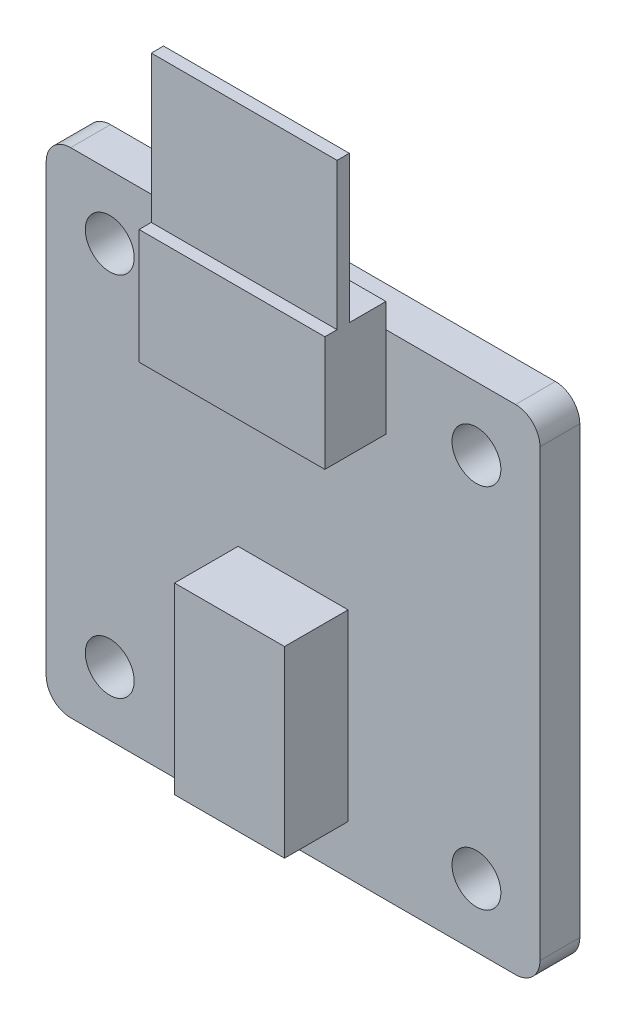
SolidWorks part; units mm, degrees
ref_plane "前视基准面" through (0, 0, 0) normal (0, 0, 1) x (1, 0, 0)
ref_plane "上视基准面" through (0, 0, 0) normal (0, 1, 0) x (1, 0, 0)
ref_plane "右视基准面" through (0, 0, 0) normal (1, 0, 0) x (0, 0, -1)
sketch "草图1" plane through (0, 0, 0) normal (0, 0, 1) x (1, 0, 0)
  line L1 (-10.1, 10.1) -> (10.1, 10.1)
  line L2 (-10.1, 10.1) -> (-10.1, -10.1)
  line L3 (-10.1, -10.1) -> (10.1, -10.1)
  line L4 (10.1, 10.1) -> (10.1, -10.1)
  line L5 (-10.1, 10.1) -> (10.1, -10.1) construction
  line L6 (-10.1, -10.1) -> (10.1, 10.1) construction
  point P0 (0, 0)
  dimension "D1" = 20.2
extrude "凸台-拉伸1" add sketch "草图1" along normal blind 1.63
fillet "圆角1" radius 1 4 edges at (10.1, -10.1, 0.815) (10.1, 10.1, 0.815) (-10.1, 10.1, 0.815) (-10.1, -10.1, 0.815)
sketch "草图2" plane through (0, 0, 1.63) normal (0, 0, 1) x (1, 0, 0)
  circle A1 centre (-7.5, 7.5) radius 1
  circle A2 centre (7.5, 7.5) radius 1
  circle A3 centre (7.5, -7.5) radius 1
  circle A4 centre (-7.5, -7.5) radius 1
  point P13 (0, 0)
  dimension "D1" = 7.5
  dimension "D2" = 7.5
  dimension "D3" = 4
extrude "切除-拉伸1" cut sketch "草图2" against normal through all and the other way blind 5
sketch "草图3" plane through (0, 0, 1.63) normal (0, 0, 1) x (1, 0, 0)
  line L4 (0, 6.4) -> (3.8, 6.4)
  line L5 (3.8, 6.4) -> (3.8, 11.1)
  line L6 (3.8, 11.1) -> (-3.8, 11.1)
  line L7 (-3.8, 11.1) -> (-3.8, 6.4)
  line L8 (-3.8, 6.4) -> (0, 6.4)
extrude "凸台-拉伸2" add sketch "草图3" along normal blind 2.5
sketch "草图4" plane through (0, 0, 1.63) normal (0, 0, 1) x (1, 0, 0)
  line L2 (0, -8.1) -> (-2.25, -8.1)
  line L3 (-2.25, -8.1) -> (-2.25, -0.6)
  line L4 (-2.25, -0.6) -> (2.25, -0.6)
  line L5 (2.25, -0.6) -> (2.25, -8.1)
  line L6 (2.25, -8.1) -> (0, -8.1)
extrude "凸台-拉伸3" add sketch "草图4" along normal blind 2.6
sketch "草图5" plane through (0, 0, 1.63) normal (0, 0, 1) x (1, 0, 0)
  line L8 (-3.8, 6.4) -> (-3.8, 10.1)
  line L9 (-3.8, 10.1) -> (-9.1, 10.1)
  line L10 (-10.1, 9.1) -> (-10.1, -9.1)
  line L11 (-9.1, -10.1) -> (9.1, -10.1)
  line L12 (10.1, -9.1) -> (10.1, 9.1)
  line L13 (9.1, 10.1) -> (3.8, 10.1)
  line L14 (3.8, 10.1) -> (3.8, 6.4)
  line L15 (3.8, 6.4) -> (-3.8, 6.4)
  line L16 (-3.8, 6.4) -> (-3.8, 10.1)
  line L17 (-3.8, 10.1) -> (-9.1, 10.1)
  line L18 (-10.1, 9.1) -> (-10.1, -9.1)
  line L19 (-9.1, -10.1) -> (9.1, -10.1)
  line L20 (10.1, -9.1) -> (10.1, 9.1)
  line L21 (9.1, 10.1) -> (3.8, 10.1)
  line L22 (3.8, 10.1) -> (3.8, 6.4)
  line L23 (3.8, 6.4) -> (-3.8, 6.4)
  circle A0 centre (-7.5, 7.5) radius 1 construction
  circle A1 centre (-7.5, 7.5) radius 1
  circle A2 centre (7.5, 7.5) radius 1 construction
  circle A3 centre (7.5, 7.5) radius 1
  arc A4 (-9.1, 10.1) -> (-10.1, 9.1) centre (-9.1, 9.1) ccw
  arc A5 (-10.1, -9.1) -> (-9.1, -10.1) centre (-9.1, -9.1) ccw
  arc A6 (9.1, -10.1) -> (10.1, -9.1) centre (9.1, -9.1) ccw
  arc A7 (10.1, 9.1) -> (9.1, 10.1) centre (9.1, 9.1) ccw
  arc A8 (-9.1, 10.1) -> (-10.1, 9.1) centre (-9.1, 9.1) ccw
  arc A9 (-10.1, -9.1) -> (-9.1, -10.1) centre (-9.1, -9.1) ccw
  arc A10 (9.1, -10.1) -> (10.1, -9.1) centre (9.1, -9.1) ccw
  arc A11 (10.1, 9.1) -> (9.1, 10.1) centre (9.1, 9.1) ccw
  circle A12 centre (7.5, -7.5) radius 1 construction
  circle A13 centre (7.5, -7.5) radius 1
  circle A14 centre (-7.5, -7.5) radius 1 construction
  circle A15 centre (-7.5, -7.5) radius 1
  dimension "D1" = 0
sketch "草图6" plane through (0, 11.1, 0) normal (0, 1, 0) x (1, 0, 0)
  line L9 (3.8, -4.03) -> (3.8, -3.53)
  line L10 (3.8, -4.13) -> (3.8, -1.63) construction
  line L11 (3.8, -3.53) -> (-3.8, -3.53)
  line L12 (-3.8, -4.13) -> (-3.8, -1.63) construction
  line L14 (-3.8, -4.03) -> (-3.8, -3.53)
  line L15 (3.8, -4.03) -> (-3.8, -4.03)
extrude "凸台-拉伸6" add sketch "草图6" along normal blind 6
sketch "草图7" plane through (0, 0, 3.53) normal (0, 0, -1) x (-1, 0, 0)
  line L4 (-3.8, 11.1) -> (3.8, 11.1)
  line L5 (3.8, 11.1) -> (3.8, 17.1)
  line L6 (3.8, 17.1) -> (-3.8, 17.1)
  line L7 (-3.8, 17.1) -> (-3.8, 11.1)
  line L8 (-3.8, 11.1) -> (3.8, 11.1)
  line L9 (3.8, 11.1) -> (3.8, 17.1)
  line L10 (3.8, 17.1) -> (-3.8, 17.1)
  line L11 (-3.8, 17.1) -> (-3.8, 11.1)
  dimension "D1" = 0
extrude "凸台-拉伸7" add sketch "草图7" along normal blind 0.4
sketch "草图8" plane through (0, 0, 4.03) normal (0, 0, 1) x (1, 0, 0)
  line L4 (-3.8, 11.1) -> (3.8, 11.1)
  line L5 (3.8, 11.1) -> (3.8, 17.1)
  line L6 (3.8, 17.1) -> (-3.8, 17.1)
  line L7 (-3.8, 17.1) -> (-3.8, 11.1)
  line L8 (-3.8, 11.1) -> (3.8, 11.1)
  line L9 (3.8, 11.1) -> (3.8, 17.1)
  line L10 (3.8, 17.1) -> (-3.8, 17.1)
  line L11 (-3.8, 17.1) -> (-3.8, 11.1)
  dimension "D1" = 0
extrude "切除-拉伸2" cut sketch "草图8" against normal blind 0.4
sketch "草图9" plane through (0, 0, 0) normal (0, 0, -1) x (-1, 0, 0)
  line L2 (0, 6.1) -> (3.4, 6.1)
  line L3 (3.4, 6.1) -> (-3.4, 6.1)
  line L4 (-3.4, 6.1) -> (-3.4, 7.7)
  line L5 (-3.4, 7.7) -> (3.4, 7.7)
  line L6 (3.4, 7.7) -> (3.4, 6.1)
extrude "凸台-拉伸8" add sketch "草图9" along normal blind 1.4 contours L6 L5 L4 L3 L2 region at (0, 6.9, 0)
ref_plane "基准面2" through (0, 0, 0) normal (-1, 0, 0) x (0, 0, 1)
ref_plane "基准面1" through (0, 0, 0) normal (-1, 0, 0) x (0, 0, 1)
extrude "切除-拉伸3" cut sketch "草图10" against normal blind 1.5
sketch "草图10" plane through (6.4149, 4.3027, 0) normal (0, 0, 1) x (1, 0, 0)
  line L8 (-9.8149, 3.3973) -> (-9.8149, 1.7973)
  line L9 (-3.0149, 3.3973) -> (-9.8149, 3.3973)
  line L10 (-3.0149, 1.7973) -> (-3.0149, 3.3973)
  line L11 (-9.8149, 1.7973) -> (-3.0149, 1.7973)
